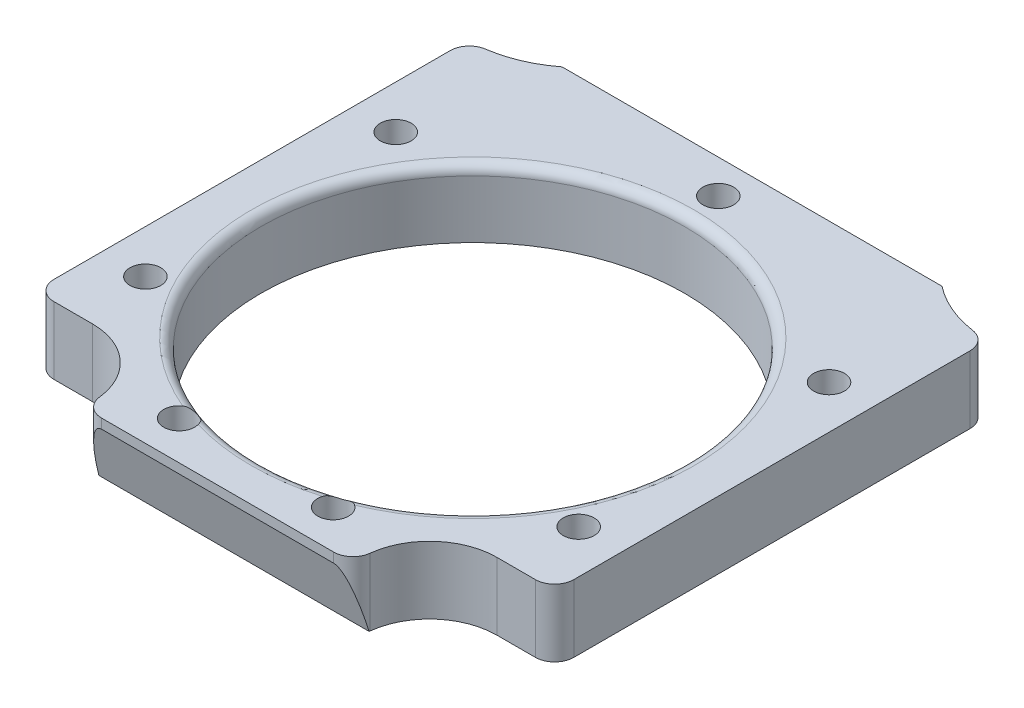
SolidWorks part; units mm, degrees
material "PBT Общее назначение"
ref_plane "Спереди" through (0, 0, 0) normal (0, 0, 1) x (1, 0, 0)
ref_plane "Сверху" through (0, 0, 0) normal (0, 1, 0) x (1, 0, 0)
ref_plane "Справа" through (0, 0, 0) normal (1, 0, 0) x (0, 0, -1)
ref_plane "Плоскость4" through (0, -5, 0) normal (0, -1, 0) x (-1, 0, 0)
sketch "Эскиз2" plane through (0, -5, 0) normal (0, -1, 0) x (-1, 0, 0)
  line L4 (-28.0557, -61) -> (-3.9443, -61)
  line L5 (-43, -9.8545) -> (-43, -51)
  line L6 (3.7313, -5.5) -> (-35.7313, -5.5)
  line L7 (11, -51) -> (11, -9.8545)
  line L8 (-28.0557, -61) -> (-3.9443, -61)
  line L9 (-43, -9.8545) -> (-43, -51)
  line L10 (3.7313, -5.5) -> (-35.7313, -5.5)
  line L11 (11, -51) -> (11, -9.8545)
  line L24 (5, -53) -> (9, -53)
  line L25 (5, -53) -> (9, -53)
  line L30 (-41, -53) -> (-37, -53)
  line L31 (-41, -53) -> (-37, -53)
  arc A10 (5, -53) -> (-1.9567, -59.2222) centre (5, -60) ccw
  arc A11 (5, -53) -> (-1.9567, -59.2222) centre (5, -60) ccw
  arc A12 (-30.0433, -59.2222) -> (-37, -53) centre (-37, -60) ccw
  arc A13 (-30.0433, -59.2222) -> (-37, -53) centre (-37, -60) ccw
  arc A17 (-41.2895, -7.8755) -> (-35.7313, -5.5) centre (-43, 3.8167) ccw
  arc A18 (3.7313, -5.5) -> (9.2895, -7.8755) centre (11, 3.8167) ccw
  arc A27 (-41.2895, -7.8755) -> (-35.7313, -5.5) centre (-43, 3.8167) ccw
  arc A28 (3.7313, -5.5) -> (9.2895, -7.8755) centre (11, 3.8167) ccw
  arc A60 (11, -9.8545) -> (9.2895, -7.8755) centre (9, -9.8545) ccw
  arc A61 (11, -9.8545) -> (9.2895, -7.8755) centre (9, -9.8545) ccw
  arc A62 (9, -53) -> (11, -51) centre (9, -51) ccw
  arc A63 (9, -53) -> (11, -51) centre (9, -51) ccw
  arc A64 (-3.9443, -61) -> (-1.9567, -59.2222) centre (-3.9443, -59) ccw
  arc A65 (-3.9443, -61) -> (-1.9567, -59.2222) centre (-3.9443, -59) ccw
  arc A66 (-30.0433, -59.2222) -> (-28.0557, -61) centre (-28.0557, -59) ccw
  arc A67 (-30.0433, -59.2222) -> (-28.0557, -61) centre (-28.0557, -59) ccw
  arc A68 (-43, -51) -> (-41, -53) centre (-41, -51) ccw
  arc A69 (-43, -51) -> (-41, -53) centre (-41, -51) ccw
  arc A70 (-41.2895, -7.8755) -> (-43, -9.8545) centre (-41, -9.8545) ccw
  arc A71 (-41.2895, -7.8755) -> (-43, -9.8545) centre (-41, -9.8545) ccw
  dimension "D1" = 0
extrude "Бобышка-Вытянуть1" add sketch "Эскиз2" along normal blind 5
sketch "Эскиз3" plane through (0, -10, 0) normal (0, -1, 0) x (1, 0, 0)
  circle A0 centre (16, 34.5) radius 22 construction
  circle A1 centre (16, 34.5) radius 22
  dimension "D1" = 44
extrude "Вырез-Вытянуть1" cut sketch "Эскиз3" against normal through all contours A1
sketch "Эскиз4" plane through (0, -10, 0) normal (0, -1, 0) x (1, 0, 0)
  circle A0 centre (38.5, 20) radius 1.6 construction
  circle A1 centre (-6.5, 20) radius 1.6 construction
  circle A2 centre (-6.5, 46) radius 1.6 construction
  circle A3 centre (38.5, 46) radius 1.6 construction
  circle A4 centre (38.5, 20) radius 1.6
  circle A5 centre (-6.5, 20) radius 1.6
  circle A6 centre (-6.5, 46) radius 1.6
  circle A7 centre (38.5, 46) radius 1.6
  circle A8 centre (16, 9) radius 1.6 construction
  circle A9 centre (24, 57) radius 1.6 construction
  circle A10 centre (8, 57) radius 1.6 construction
  circle A11 centre (24, 57) radius 1.6
  circle A12 centre (8, 57) radius 1.6
  circle A13 centre (16, 9) radius 1.6
extrude "Вырез-Вытянуть3" cut sketch "Эскиз4" against normal through all
sketch "Эскиз9" plane through (0, -10, 0) normal (0, -1, 0) x (1, 0, 0)
  line L4 (28.0557, 61) -> (3.9443, 61)
  line L5 (-11, 51) -> (-11, 9.8545)
  line L6 (-3.7313, 5.5) -> (35.7313, 5.5)
  line L7 (43, 9.8545) -> (43, 51)
  line L8 (28.0557, 61) -> (3.9443, 61)
  line L9 (-11, 51) -> (-11, 9.8545)
  line L10 (-3.7313, 5.5) -> (35.7313, 5.5)
  line L11 (43, 9.8545) -> (43, 51)
  line L18 (-5, 53) -> (-9, 53)
  line L19 (-5, 53) -> (-9, 53)
  line L20 (41, 53) -> (37, 53)
  line L21 (41, 53) -> (37, 53)
  circle A0 centre (38.5, 46) radius 1.6 construction
  circle A1 centre (24, 57) radius 1.6 construction
  circle A2 centre (38.5, 20) radius 1.6 construction
  circle A3 centre (-6.5, 20) radius 1.6 construction
  circle A4 centre (-6.5, 46) radius 1.6 construction
  circle A5 centre (8, 57) radius 1.6 construction
  circle A6 centre (16, 34.5) radius 22 construction
  circle A7 centre (38.5, 46) radius 1.6
  circle A8 centre (24, 57) radius 1.6
  circle A9 centre (38.5, 20) radius 1.6
  arc A10 (-5, 53) -> (1.9567, 59.2222) centre (-5, 60) ccw
  arc A11 (-5, 53) -> (1.9567, 59.2222) centre (-5, 60) ccw
  arc A12 (30.0433, 59.2222) -> (37, 53) centre (37, 60) ccw
  arc A13 (30.0433, 59.2222) -> (37, 53) centre (37, 60) ccw
  arc A14 (-3.7313, 5.5) -> (-9.2895, 7.8755) centre (-11, -3.8167) ccw
  arc A15 (41.2895, 7.8755) -> (35.7313, 5.5) centre (43, -3.8167) ccw
  circle A16 centre (16, 9) radius 1.6 construction
  circle A17 centre (16, 9) radius 1.6
  arc A24 (-3.7313, 5.5) -> (-9.2895, 7.8755) centre (-11, -3.8167) ccw
  arc A25 (41.2895, 7.8755) -> (35.7313, 5.5) centre (43, -3.8167) ccw
  arc A28 (-9, 53) -> (-11, 51) centre (-9, 51) ccw
  arc A29 (-9, 53) -> (-11, 51) centre (-9, 51) ccw
  circle A30 centre (-6.5, 20) radius 1.6
  circle A31 centre (-6.5, 46) radius 1.6
  circle A32 centre (8, 57) radius 1.6
  circle A33 centre (16, 34.5) radius 22
  arc A34 (-11, 9.8545) -> (-9.2895, 7.8755) centre (-9, 9.8545) ccw
  arc A35 (-11, 9.8545) -> (-9.2895, 7.8755) centre (-9, 9.8545) ccw
  arc A36 (41.2895, 7.8755) -> (43, 9.8545) centre (41, 9.8545) ccw
  arc A37 (41.2895, 7.8755) -> (43, 9.8545) centre (41, 9.8545) ccw
  arc A38 (43, 51) -> (41, 53) centre (41, 51) ccw
  arc A39 (43, 51) -> (41, 53) centre (41, 51) ccw
  arc A40 (30.0433, 59.2222) -> (28.0557, 61) centre (28.0557, 59) ccw
  arc A41 (30.0433, 59.2222) -> (28.0557, 61) centre (28.0557, 59) ccw
  arc A42 (3.9443, 61) -> (1.9567, 59.2222) centre (3.9443, 59) ccw
  arc A43 (3.9443, 61) -> (1.9567, 59.2222) centre (3.9443, 59) ccw
  dimension "D1" = 0
extrude "Бобышка-Вытянуть2" add sketch "Эскиз9" along normal blind 2
sketch "Эскиз11" plane through (0, -12, 0) normal (0, -1, 0) x (1, 0, 0)
  line L0 (16, 5.5) -> (16, 61) construction
  line L1 (-3.7313, 5.5) -> (35.7313, 5.5) construction
  line L2 (28.0557, 61) -> (3.9443, 61) construction
ref_plane "sym" through (16, 0, 0) normal (1, 0, 0) x (0, 0, 1)
fillet "Скругление1" radius 1 1 edges at (16, -5, 12.5)
sketch "Эскиз12" plane through (16, 0, 0) normal (1, 0, 0) x (0, 0, 1)
  line L0 (61, 12) -> (61, 5) construction
  line L1 (61, 12) -> (61, 6)
  line L2 (61, 6) -> (59.3, 12)
  line L3 (5.5, 12) -> (61, 12) construction
  line L4 (59.3, 12) -> (61, 12)
  dimension "D1" = 1.7
  dimension "D2" = 6
extrude "Вырез-Вытянуть4" cut sketch "Эскиз12" against normal through all and the other way through all
